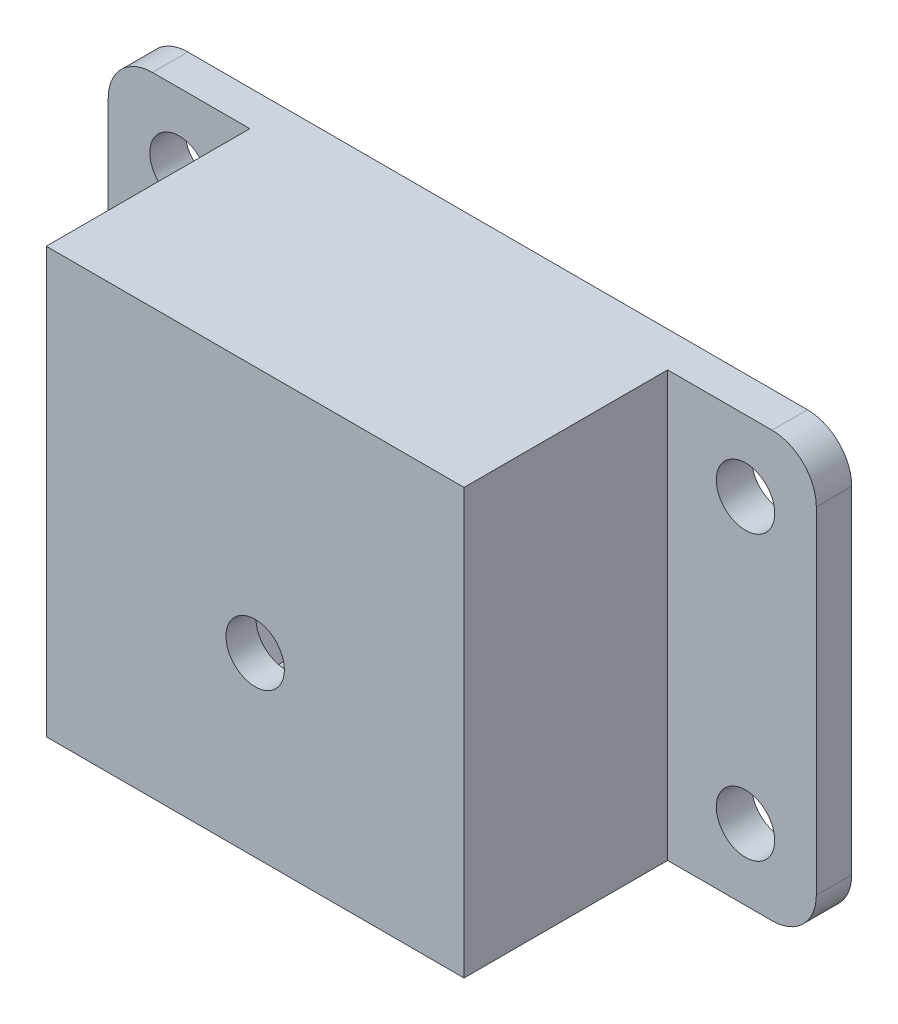
SolidWorks part; units mm, degrees
ref_plane "Front Plane" through (0, 0, 0) normal (1, 0, 0) x (0, 1, 0)
ref_plane "Top Plane" through (0, 0, 0) normal (0, 0, 1) x (0, 1, 0)
ref_plane "Right Plane" through (0, 0, 0) normal (0, 1, 0) x (-1, 0, 0)
sketch "Sketch1" plane through (0, 0, 0) normal (0, 0, 1) x (0, 1, 0)
  line L0 (-24, 12.4) -> (-4, 12.4)
  line L1 (0, 0) -> (-24, 0)
  line L2 (0, 0) -> (0, 40)
  line L3 (0, 40) -> (-24, 40)
  line L4 (-24, 0) -> (-24, 12.4)
  line L5 (-4, 12.4) -> (-4, 28)
  line L6 (-4, 28) -> (-24, 28)
  line L7 (-24, 28) -> (-24, 40)
  circle A0 centre (-20, 4) radius 1.65
  circle A1 centre (-4, 4) radius 1.65
  circle A2 centre (-4, 36) radius 1.65
  circle A3 centre (-20, 36) radius 1.65
  dimension "D1" = 3.3
  dimension "D4" = 20
  dimension "D5" = 4
  dimension "D7" = 20
  dimension "D9" = 32
  dimension "D11" = 4
  dimension "D12" = 20
  dimension "D3" = 4
  dimension "D10" = 4
  dimension "D2" = 15.6
  dimension "D6" = 4
  dimension "D8" = 12
extrude "Boss-Extrude1" add sketch "Sketch1" along normal blind 2
sketch "Sketch2" plane through (0, 0, 2) normal (0, 0, 1) x (1, 0, 0)
  line L0 (-28, -24) -> (-28, -4)
  line L1 (-28, -4) -> (-12.4, -4)
  line L2 (-12.4, -4) -> (-12.4, -24)
  line L3 (-12.4, -24) -> (-8.4, -24)
  line L4 (-12.4, -24) -> (0, -24) construction
  line L5 (-8.4, -24) -> (-8.4, 0)
  line L6 (0, 0) -> (-40, 0) construction
  line L7 (-8.4, 0) -> (-32, 0)
  line L8 (-32, 0) -> (-32, -24)
  line L9 (-40, -24) -> (-28, -24) construction
  line L10 (-32, -24) -> (-28, -24)
  dimension "D1" = 4
  dimension "D2" = 4
extrude "Boss-Extrude2" add sketch "Sketch2" along normal blind 5.5
sketch "Sketch3" plane through (0, 0, 7.5) normal (0, 0, 1) x (1, 0, 0)
  line L1 (-32, 0) -> (-8.4, 0)
  line L2 (-32, 0) -> (-32, -24)
  line L3 (-32, -24) -> (-8.4, -24)
  line L4 (-8.4, 0) -> (-8.4, -24)
  circle A0 centre (-20.2, -14) radius 1.65
  point P8 (-20.2, 0)
  dimension "D1" = 3.3
  dimension "D2" = 10
extrude "Boss-Extrude3" add sketch "Sketch3" along normal blind 6
sketch "Sketch4" plane through (0, 0, 13.5) normal (0, 0, 1) x (1, 0, 0)
  line L1 (-16.8514, -14) -> (-18.5257, -11.1)
  line L2 (-18.5257, -11.1) -> (-21.8743, -11.1)
  line L3 (-21.8743, -11.1) -> (-23.5486, -14)
  line L4 (-23.5486, -14) -> (-21.8743, -16.9)
  line L5 (-21.8743, -16.9) -> (-18.5257, -16.9)
  line L6 (-18.5257, -16.9) -> (-16.8514, -14)
  circle A0 centre (-20.2, -14) radius 2.9 construction
  dimension "D1" = 5.8
extrude "Cut-Extrude1" cut sketch "Sketch4" against normal blind 2.6 from offset 1.7 offset against normal yes
fillet "Fillet1" radius 2.5 4 edges at (0, -24, 1) (0, 0, 1) (-40, 0, 1) (-40, -24, 1)
